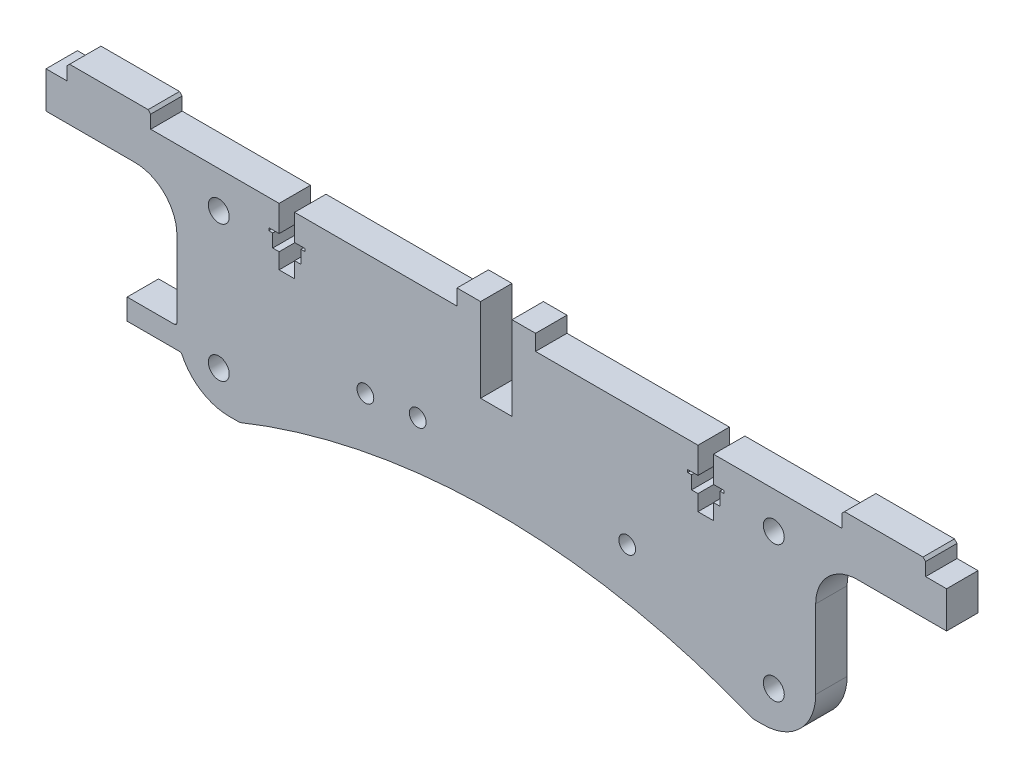
SolidWorks part; units mm, degrees
material "Oak"
ref_plane "Front Plane" through (0, 0, 0) normal (0, 0, 1) x (1, 0, 0)
ref_plane "Top Plane" through (0, 0, 0) normal (0, 1, 0) x (1, 0, 0)
ref_plane "Right Plane" through (0, 0, 0) normal (1, 0, 0) x (0, 0, -1)
sketch "Sketch1" plane through (0, 0, 0) normal (0, 0, 1) x (1, 0, 0)
  line L0 (0, -43.0686) -> (0, 56.6488) construction
  line L1 (-7.5, 20) -> (-66, 20)
  line L2 (49, 10.5) -> (65, 10.5) construction
  line L3 (49, 10.5) -> (49, -10.5) construction
  line L4 (49, -10.5) -> (65, -10.5) construction
  line L5 (65, 10.5) -> (65, -10.5) construction
  line L6 (66, 20) -> (66, 23)
  line L7 (66, 23) -> (82, 23)
  line L8 (86, 20) -> (86, 13)
  line L9 (-7.5, 20) -> (-7.5, 23)
  line L10 (61, -20) -> (49, -20)
  line L11 (49, 10.5) -> (65, -10.5) construction
  line L12 (65, 10.5) -> (49, -10.5) construction
  line L13 (-65, 10.5) -> (-49, -10.5) construction
  line L14 (-49, 10.5) -> (-65, -10.5) construction
  line L15 (-65, 10.5) -> (-65, -10.5) construction
  line L16 (-49, -10.5) -> (-65, -10.5) construction
  line L17 (-49, 10.5) -> (-49, -10.5) construction
  line L18 (-49, 10.5) -> (-65, 10.5) construction
  line L19 (-7.5, 23) -> (-3, 23)
  line L20 (-69, 13) -> (-86, 13)
  line L21 (-82, 20) -> (-82, 23)
  line L22 (-86, 20) -> (-82, 20)
  line L23 (7.5, 20) -> (7.5, 23)
  line L24 (7.5, 23) -> (3, 23)
  line L25 (7.5, 20) -> (66, 20)
  line L26 (86, 20) -> (82, 20)
  line L27 (3, 23) -> (3, 7)
  line L28 (-57, 0) -> (57, 0) construction
  line L29 (3, 7) -> (-3, 7)
  line L30 (82, 20) -> (82, 23)
  line L31 (-86, 20) -> (-86, 13)
  line L32 (-66, 23) -> (-82, 23)
  line L33 (-49, -20) -> (-61, -20)
  line L34 (-66, 20) -> (-66, 23)
  line L35 (-3, 23) -> (-3, 7)
  line L43 (-61, -20) -> (-61, 5)
  line L45 (61, -20) -> (61, 5)
  line L46 (69, 13) -> (86, 13)
  arc A0 (49, -20) -> (-49, -20) centre (0, -141.6184) ccw
  arc A1 (-69, 13) -> (-61, 5) centre (-69, 5) cw
  arc A2 (69, 13) -> (61, 5) centre (69, 5) ccw
  point P7 (-57, 0)
  point P9 (57, 0)
  point P20 (0, 0)
  point P24 (0, 40)
  point P25 (0, -10.5)
  point P27 (73.331, 42)
  point P30 (0, 40)
  point P31 (68.331, 20)
  point P32 (99.8, 42)
  point P38 (98.8347, 49.7973)
  point P54 (0, 7)
  dimension "D8" = 7
  dimension "D9" = 8
  dimension "D1" = 16
  dimension "D2" = 65
  dimension "D3" = 86
  dimension "D4" = 4
  dimension "D5" = 15
  dimension "D6" = 7
  dimension "D7" = 21
  dimension "D10" = 3
  dimension "D11" = 20
  dimension "D12" = 20
  dimension "D13" = 6
  dimension "D14" = 122
  dimension "D16" = 20
extrude "Boss-Extrude1" add sketch "Sketch1" along normal blind 6
sketch "Sketch2" plane through (0, 0, 6) normal (0, 0, 1) x (1, 0, 0)
  line L0 (0, 0) -> (0, -20) construction
  line L1 (-61, -20) -> (-49, -20) construction
  line L2 (-25, -3.2) -> (25, -3.2) construction
  line L3 (0, 0) -> (0, -3.2) construction
  line L4 (66, 20) -> (7.5, 20) construction
  line L7 (45, -8) -> (45, 8) construction
  line L8 (45, -8) -> (61, -8) construction
  line L9 (45, 8) -> (61, 8) construction
  line L10 (61, -8) -> (61, 8) construction
  line L11 (45, -8) -> (61, 8) construction
  line L12 (45, 8) -> (61, -8) construction
  circle A0 centre (53, -13) radius 2
  circle A1 centre (53, 13) radius 2
  circle A2 centre (25, -3.2) radius 1.6
  circle A3 centre (-25, -3.2) radius 1.6
  point P7 (53, 0)
  dimension "D2" = 4
  dimension "D3" = 20
  dimension "D5" = 3.2
  dimension "D1" = 53
  dimension "D4" = 13
  dimension "D6" = 50
  dimension "D7" = 16
  dimension "D8" = 3.2
  dimension "D16" = 13
extrude "Cut-Extrude1" cut sketch "Sketch2" against normal through all
mirror "Mirror1" about plane through (0, 0, 0) normal (1, 0, 0) of "Cut-Extrude1"
chamfer "Chamfer1" distance 0.5 angle 45 4 edges at (66, 23, 3) (82, 23, 3) (-66, 23, 3) (-82, 23, 3)
fillet "Fillet1" radius 10 2 edges at (-61, -20, 3) (61, -20, 3)
sketch "Sketch3" plane through (0, 0, 6) normal (0, 0, 1) x (1, 0, 0)
  line L0 (-61, 5) -> (-61, -10) construction
  line L1 (-57.0317, -10) -> (-70.5, -10)
  line L2 (-57.0317, -10) -> (-57.0317, -14)
  line L3 (-57.0317, -14) -> (-70.5, -14)
  line L4 (-70.5, -10) -> (-70.5, -14)
  line L5 (-51, -20) -> (-49, -20) construction
  dimension "D1" = 9.5
  dimension "D2" = 6
  dimension "D3" = 4
extrude "Boss-Extrude3" add sketch "Sketch3" against normal through all
sketch "Sketch4" plane through (0, 0, 6) normal (0, 0, 1) x (1, 0, 0)
  line L0 (0, 0) -> (0, 22.5154) construction
  line L1 (-40, 20) -> (-40, 9) construction
  line L2 (-7.5, 20) -> (-66, 20) construction
  line L3 (-41.48, 20) -> (-41.48, 15)
  line L4 (-41.48, 15) -> (-43.45, 15)
  line L5 (-43.45, 15) -> (-43.45, 14.5)
  line L6 (-43.45, 14.5) -> (-42.7, 14.5)
  line L7 (-42.7, 14.5) -> (-42.7, 12)
  line L8 (-42.7, 12) -> (-41.48, 12)
  line L9 (-41.48, 12) -> (-41.48, 9)
  line L10 (-41.48, 9) -> (-38.52, 9)
  line L11 (-38.52, 12) -> (-38.52, 9)
  line L12 (-37.3, 12) -> (-38.52, 12)
  line L13 (-37.3, 14.5) -> (-37.3, 12)
  line L14 (-36.55, 14.5) -> (-37.3, 14.5)
  line L15 (-36.55, 15) -> (-36.55, 14.5)
  line L16 (-38.52, 15) -> (-36.55, 15)
  line L17 (-38.52, 20) -> (-38.52, 15)
  line L18 (40, 20) -> (40, 9) construction
  line L19 (38.52, 20) -> (38.52, 15)
  line L20 (38.52, 15) -> (36.55, 15)
  line L21 (36.55, 15) -> (36.55, 14.5)
  line L22 (36.55, 14.5) -> (37.3, 14.5)
  line L23 (37.3, 14.5) -> (37.3, 12)
  line L24 (37.3, 12) -> (38.52, 12)
  line L25 (38.52, 12) -> (38.52, 9)
  line L26 (41.48, 9) -> (38.52, 9)
  line L27 (41.48, 12) -> (41.48, 9)
  line L28 (42.7, 12) -> (41.48, 12)
  line L29 (42.7, 14.5) -> (42.7, 12)
  line L30 (43.45, 14.5) -> (42.7, 14.5)
  line L31 (43.45, 15) -> (43.45, 14.5)
  line L32 (41.48, 15) -> (43.45, 15)
  line L33 (41.48, 20) -> (41.48, 15)
  line L34 (-41.48, 20) -> (-38.52, 20)
  line L35 (38.52, 20) -> (41.48, 20)
  dimension "D1" = 0.5
  dimension "D2" = 2.5
  dimension "D3" = 3
  dimension "D4" = 11
  dimension "D5" = 2.96
  dimension "D6" = 6.9
  dimension "D7" = 5.4
  dimension "D8" = 40
extrude "Cut-Extrude2" cut sketch "Sketch4" against normal through all
fillet "Fillet2" radius 0.5 2 edges at (-60.1652, -14, 3) (-61, -10, 3)
sketch "Sketch5" plane through (0, 0, 6) normal (0, 0, 1) x (1, 0, 0)
  circle A0 centre (-15, -2.2) radius 1.6
  circle A1 centre (-25, -3.2) radius 1.6 construction
  point P2 (-25, -3.2)
  dimension "D1" = 10
  dimension "D2" = 1
extrude "Cut-Extrude3" cut sketch "Sketch5" against normal through all
equation "\"bed-plate-thickness\"=3"
equation "\"D1@Boss-Extrude1\"=\"y-rib-thickness\""
equation "\"D10@Sketch1\"=\"bed-plate-thickness\""
equation "\"D13@Sketch1\"=\"y-cross-rib-thickness\""
equation "\"y-cross-rib-thickness\"=6"
equation "\"y-rib-thickness\"=6"
equation "\"x-plate-thickness\"=5"
equation "\"rod-diameter\"=12"
equation "\"t-nut-hole-diameter\"=3"
equation "\"y-plate-thickness\"=5"
equation "\"D8@Sketch2\"=9-(11.6/2)"
